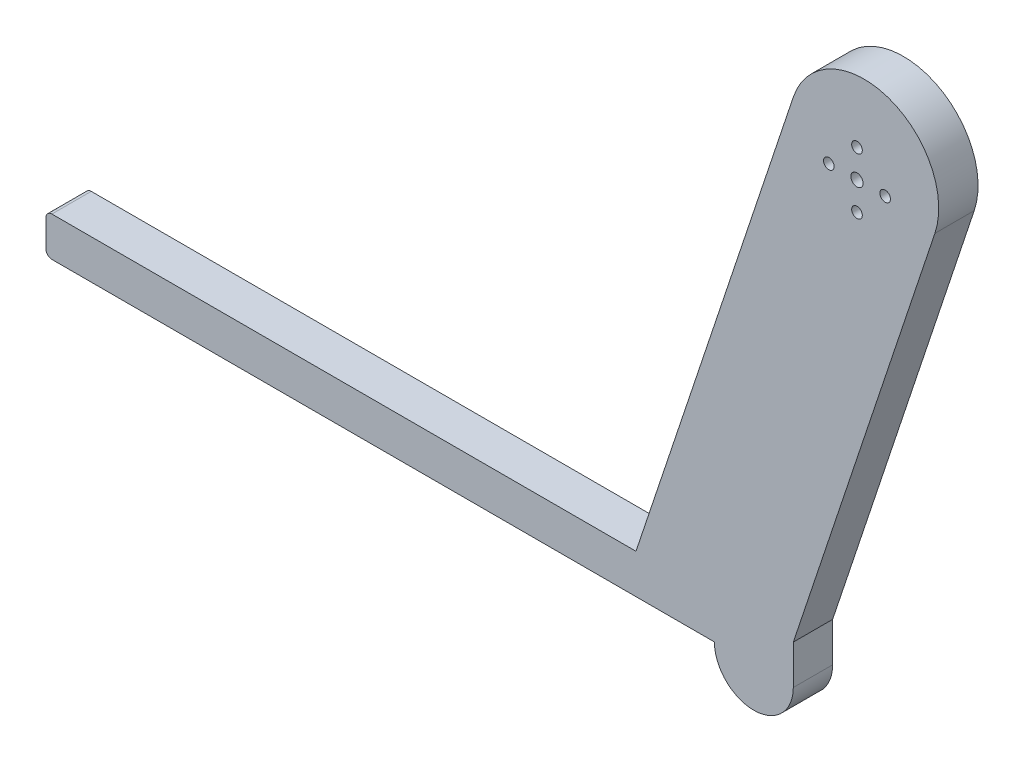
SolidWorks part; units mm, degrees
ref_plane "前视基准面" through (0, 0, 0) normal (0, 0, 1) x (1, 0, 0)
ref_plane "上视基准面" through (0, 0, 0) normal (0, 1, 0) x (1, 0, 0)
ref_plane "右视基准面" through (0, 0, 0) normal (1, 0, 0) x (0, 0, -1)
sketch "草图1" plane through (0, 0, 0) normal (0, 0, 1) x (1, 0, 0)
  line L4 (-150, -1.5) -> (-150, -8.5)
  line L5 (-148.5, -10) -> (19.9372, -10)
  line L6 (40, -8.5) -> (40, 0)
  line L7 (0, 0) -> (40, 120)
  line L8 (40, 0) -> (76, 108)
  line L9 (-148.5, 0) -> (40, 0)
  line L10 (40, -8.5) -> (40, -10)
  line L11 (0, 0) -> (40, 0)
  arc A1 (-150, -8.5) -> (-148.5, -10) centre (-148.5, -8.5) ccw
  arc A2 (-148.5, 0) -> (-150, -1.5) centre (-148.5, -1.5) ccw
  circle A3 centre (56.1909, 109.8725) radius 1.55
  circle A6 centre (63.3499, 109.8725) radius 1.35
  circle A7 centre (56.1909, 117.0315) radius 1.35
  circle A8 centre (56.1909, 102.7135) radius 1.35
  circle A9 centre (49.0319, 109.8725) radius 1.35
  circle A10 centre (56.1909, 109.8725) radius 9.8
  arc A11 (19.9372, -10) -> (40, -10) centre (29.9686, -10) ccw
  arc A13 (40, 120) -> (76, 108) centre (58, 114) cw
extrude "凸台-拉伸1" add sketch "草图1" along normal blind 10 contours L6 L10 A11 L5 A1 L4 A2 L9
extrude "凸台-拉伸2" add sketch "草图1<6>" along normal blind 10 contours L11 L7 A13 L8
sketch "草图1<6>" plane through (0, 0, 0) normal (0, 0, 1) x (1, 0, 0) same geometry as "草图1"
extrude "切除-拉伸1" cut sketch "草图1<8>" along normal blind 10 contours A6 | A8 | A9 | A7
sketch "草图1<8>" plane through (0, 0, 0) normal (0, 0, 1) x (1, 0, 0) same geometry as "草图1"
extrude "切除-拉伸2" cut sketch "草图1<9>" along normal blind 10 contours A3
sketch "草图1<9>" plane through (0, 0, 0) normal (0, 0, 1) x (1, 0, 0) same geometry as "草图1"
extrude "切除-拉伸3" cut sketch "草图1<10>" along normal blind 2 contours A10
sketch "草图1<10>" plane through (0, 0, 0) normal (0, 0, 1) x (1, 0, 0) same geometry as "草图1"
